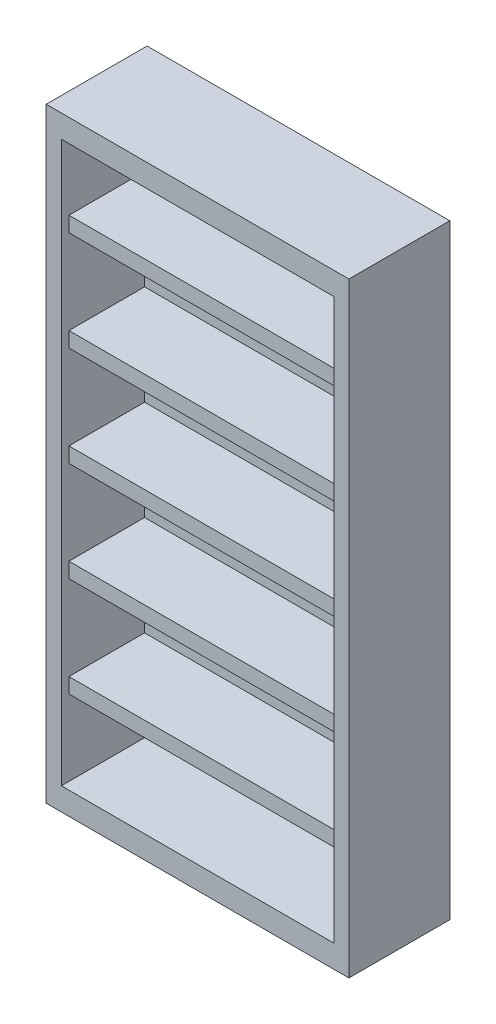
SolidWorks part; units mm, degrees
ref_plane "Front Plane" through (0, 0, 0) normal (0, 0, 1) x (1, 0, 0)
ref_plane "Top Plane" through (0, 0, 0) normal (0, 1, 0) x (1, 0, 0)
ref_plane "Right Plane" through (0, 0, 0) normal (1, 0, 0) x (0, 0, -1)
sketch "Sketch1" plane through (0, 0, 0) normal (0, 1, 0) x (1, 0, 0)
  line L1 (-50, 16.6667) -> (50, 16.6667)
  line L2 (-50, 16.6667) -> (-50, -16.6667)
  line L3 (-50, -16.6667) -> (50, -16.6667)
  line L4 (50, 16.6667) -> (50, -16.6667)
  line L5 (-50, 16.6667) -> (50, -16.6667) construction
  line L6 (-50, -16.6667) -> (50, 16.6667) construction
  point P0 (0, 0)
  dimension "D1" = 100
  dimension "D2" = 33.3333
extrude "Boss-Extrude1" add sketch "Sketch1" along normal mid plane 200
sketch "Sketch2" plane through (0, 0, 16.6667) normal (0, 0, 1) x (1, 0, 0)
  line L0 (50, 100) -> (50, -100) construction
  line L1 (-45, 92.5) -> (45, 92.5)
  line L2 (-45, 92.5) -> (-45, -92.5)
  line L3 (-45, -92.5) -> (45, -92.5)
  line L4 (45, 92.5) -> (45, -92.5)
  line L5 (-45, 92.5) -> (45, -92.5) construction
  line L6 (-45, -92.5) -> (45, 92.5) construction
  line L7 (-50, -100) -> (50, -100) construction
  point P0 (0, 0)
  dimension "D1" = 5
  dimension "D2" = 7.5
extrude "Cut-Extrude1" cut sketch "Sketch2" against normal blind 27.5
sketch "Sketch3" plane through (0, 0, -10.8333) normal (0, 0, 1) x (1, 0, 0)
  line L0 (45, -92.5) -> (45, 92.5) construction
  line L1 (45, -62.5) -> (-45, -62.5)
  line L2 (45, -62.5) -> (45, -67.5)
  line L3 (45, -67.5) -> (-45, -67.5)
  line L4 (-45, -62.5) -> (-45, -67.5)
  line L5 (-45, 92.5) -> (-45, -92.5) construction
  line L6 (-45, -92.5) -> (45, -92.5) construction
  line L7 (45, -29.5) -> (-45, -29.5)
  line L8 (45, -34.5) -> (-45, -34.5)
  line L9 (45, -29.5) -> (45, -34.5)
  line L10 (-45, -29.5) -> (-45, -34.5)
  line L11 (45, 3.5) -> (-45, 3.5)
  line L12 (45, -1.5) -> (-45, -1.5)
  line L13 (45, 3.5) -> (45, -1.5)
  line L14 (-45, 3.5) -> (-45, -1.5)
  line L15 (45, 36.5) -> (-45, 36.5)
  line L16 (45, 31.5) -> (-45, 31.5)
  line L17 (45, 36.5) -> (45, 31.5)
  line L18 (-45, 36.5) -> (-45, 31.5)
  line L19 (45, 69.5) -> (-45, 69.5)
  line L20 (45, 64.5) -> (-45, 64.5)
  line L21 (45, 69.5) -> (45, 64.5)
  line L22 (-45, 69.5) -> (-45, 64.5)
  dimension "D1" = 25
  dimension "D2" = 5
  dimension "D4" = 33
  dimension "D3" = 5
extrude "Boss-Extrude2" add sketch "Sketch3" along normal blind 25
